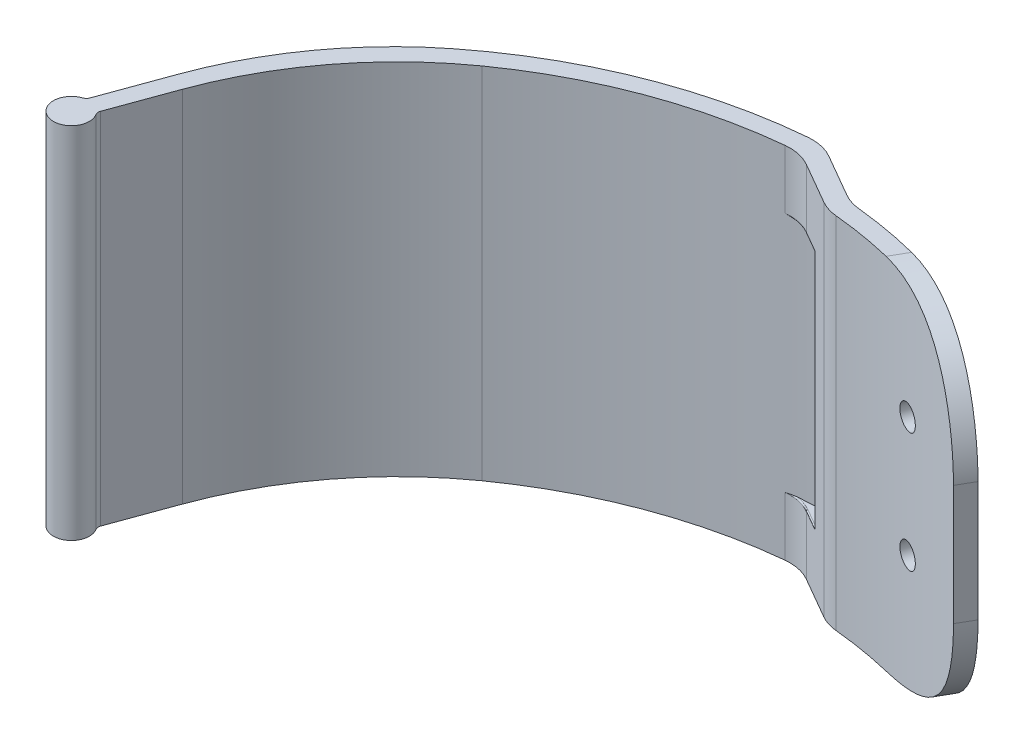
SolidWorks part; units mm, degrees
material "Silicon Rubber"
ref_plane "Front Plane" through (0, 0, 0) normal (0, 0, 1) x (1, 0, 0)
ref_plane "Top Plane" through (0, 0, 0) normal (0, 1, 0) x (1, 0, 0)
ref_plane "Right Plane" through (0, 0, 0) normal (1, 0, 0) x (0, 0, -1)
sketch "Sketch2" plane through (0, 0, 0) normal (0, 1, 0) x (1, 0, 0)
  line L0 (0, 0) -> (0, 40.4588) construction
  line L1 (0, 0) -> (-32.8892, 11.9707) construction
  line L2 (0, 0) -> (20.2294, 35.0384) construction
  line L3 (0, 0) -> (-20.2294, 35.0384) construction
  line L4 (-32.8892, 11.9707) -> (-38.0189, 13.8377) construction
  line L5 (-34.7493, 12.6477) -> (-36.1588, 13.1607) construction
  line L6 (-34.7493, 12.6477) -> (-34.9203, 12.1779)
  line L8 (-36.7997, 12.8619) -> (-34.4505, 12.0069) construction
  line L9 (-35.4541, 12.9042) -> (-36.159, 10.9673) construction
  line L10 (0, 0) -> (32.8892, 11.9707) construction
  line L11 (32.8892, 11.9707) -> (38.0189, 13.8377) construction
  line L12 (0, 36.9794) -> (0, 38.4794) construction
  line L13 (-2.4871, 39.1653) -> (2.4871, 36.2935) construction
  line L15 (-34.7493, 12.6477) -> (-31.1105, 22.6451)
  line L16 (0, 38.4794) -> (0, 39.9794) construction
  line L17 (0, 36.9794) -> (0, 35.4794) construction
  line L18 (-0.375, 37.0799) -> (0.375, 38.3789) construction
  line L19 (-2.284, 39.9141) -> (3.0118, 36.8566)
  line L20 (-2.6418, 38.3886) -> (2.5569, 35.3872)
  line L21 (18.4897, 32.0251) -> (17.7397, 30.7261)
  line L22 (-36.3298, 12.6909) -> (-32.4484, 23.3549)
  circle A0 centre (0, 0) radius 35 construction
  circle A1 centre (0, 0) radius 40.4588 construction
  arc A2 (-36.3298, 12.6909) -> (-36.6395, 12.3882) centre (-36.7997, 12.8619) cw
  arc A3 (-34.9203, 12.1779) -> (-34.8776, 11.747) centre (-34.4505, 12.0069) ccw
  arc A4 (-34.8776, 11.747) -> (-36.6395, 12.3882) centre (-36.159, 10.9673) cw
  arc A5 (35.4541, 12.9042) -> (-18.8647, 32.6746) centre (0, 0) ccw construction
  arc A6 (0, 38.4794) -> (-36.1588, 13.1607) centre (0, 0) ccw construction
  arc A7 (0, 39.9794) -> (-32.4484, 23.3549) centre (0, 0) ccw construction
  arc A8 (0, 36.9794) -> (18.4897, 32.0251) centre (0, 0) cw construction
  arc A9 (0, 35.4794) -> (17.7397, 30.7261) centre (0, 0) cw construction
  arc A10 (2.5569, 35.3872) -> (17.7397, 30.7261) centre (0, 0) cw
  arc A11 (3.0118, 36.8566) -> (18.4897, 32.0251) centre (0, 0) cw
  arc A12 (-31.1105, 22.6451) -> (-2.6418, 38.3886) centre (0, 0) cw
  arc A13 (-32.4484, 23.3549) -> (-2.284, 39.9141) centre (0, 0) cw
  point P12 (-35.4541, 12.9042)
  point P27 (0, 37.7294)
  point P30 (0, 37.7294)
  point P38 (0, 37.7294)
  dimension "D1" = 70
  dimension "D2" = 80.9177
  dimension "D8" = 0.5
  dimension "D9" = 0.5
  dimension "D10" = 1.5
  dimension "D3" = 70
  dimension "D4" = 30
  dimension "D5" = 30
  dimension "D6" = 1.5
  dimension "D11" = 70
  dimension "D12" = 1.5
  dimension "D13" = 60
  dimension "D14" = 1.5
  dimension "D15" = 1.5
  dimension "D16" = 1.5
  dimension "D7" = 0.5
extrude "Boss-Extrude1" add sketch "Sketch2" along normal blind 15 and the other way blind 15
sketch "Sketch3" plane through (0, 0, 0) normal (0, 1, 0) x (1, 0, 0)
  line L0 (-2.284, 39.9141) -> (3.0118, 36.8566) construction
  line L1 (-2.6418, 38.3886) -> (2.5569, 35.3872) construction
  line L2 (0.2019, 38.4789) -> (3.0118, 36.8566)
  line L3 (-2.6418, 38.3886) -> (-0.2, 36.9789)
  arc A0 (-2.6418, 38.3886) -> (0.2019, 38.4789) centre (0, 0) cw
  arc A1 (3.0118, 36.8566) -> (-0.2, 36.9789) centre (0, 0) ccw
extrude "Cut-Extrude1" cut sketch "Sketch3" against normal blind 10 and the other way blind 10
fillet "Fillet3" radius 3.75 6 edges at (2.5569, 0, -35.3872) (-2.6418, 12.5, -38.3886) (-2.6418, -12.5, -38.3886) (3.0118, -12.5, -36.8566) (-2.284, 0, -39.9141) (3.0118, 12.5, -36.8566)
fillet "Fillet4" radius 0.1 10 edges at (3.0203, 10, -36.9472) (1.2512, 10, -37.8731) (-0.9115, 10, -37.3896) (-2.7113, 10, -38.2194) (-0.9115, -10, -37.3896) (-2.7113, -10, -38.2194) (3.0203, -10, -36.9472) (1.2512, -10, -37.8731) (-0.2, 0, -36.9789) (0.2019, 0, -38.4789)
fillet "Fillet5" radius 30 2 edges at (-31.1105, 0, -22.6451) (-32.4484, 0, -23.3549)
sketch "Sketch4" plane through (0, 0, 0) normal (0, 1, 0) x (1, 0, 0)
  line L0 (0, 0) -> (0, 40.4588) construction
  line L1 (0, 0) -> (12.4138, 38.5073) construction
  circle A0 centre (0, 0) radius 40.4588 construction
  dimension "D1" = 17.868
ref_plane "Plane1" through (11.3462, 0, -35.1958) normal (0.3068, 0, -0.9518) x (-0.9518, 0, -0.3068)
sketch "Sketch7" plane through (11.3462, 0, -35.1958) normal (0.3068, 0, -0.9518) x (-0.9518, 0, -0.3068)
  line L0 (0, -5) -> (0, 5) construction
  circle A0 centre (0, 5) radius 1
  circle A1 centre (0, -5) radius 1
  point P4 (0, 0)
  dimension "D2" = 2
  dimension "D3" = 2
  dimension "D1" = 10
fillet "Fillet6" radius 10 2 edges at (18.1147, -15, -31.3756) (18.1147, 15, -31.3756)
sketch "Sketch8" plane through (11.3462, 0, -35.1958) normal (0.3068, 0, -0.9518) x (-0.9518, 0, -0.3068)
  line L0 (0, -5) -> (0, 5) construction
  circle A0 centre (0, 5) radius 2
  circle A1 centre (0, -5) radius 2
  point P4 (0, 0)
  dimension "D2" = 4
  dimension "D3" = 4
  dimension "D1" = 10
extrude "Cut-Extrude2" cut sketch "Sketch7" against normal through all
extrude "Cut-Extrude3" cut sketch "Sketch8" against normal blind 0.5
equation "\"Strap Thickness\"= 1.5mm"
equation "\"Strap Clamp Diameter\"= 3mm"
equation "\"Inner Diameter\"= 70mm"
equation "\"D1@Sketch2\"=\"Inner Diameter\""
equation "\"D6@Sketch2\"=\"Strap Thickness\""
equation "\"D10@Sketch2\"=\"Strap Clamp Diameter\" / 2"
equation "\"D12@Sketch2\"=\"Strap Thickness\""
equation "\"D14@Sketch2\"=\"Strap Thickness\""
equation "\"D15@Sketch2\"=\"Strap Thickness\""
equation "\"D16@Sketch2\"=\"Strap Thickness\""
equation "\"Band Width\"= 30mm"
equation "\"D1@Boss-Extrude1\"=\"Band Width\" / 2"
equation "\"D2@Boss-Extrude1\"=\"Band Width\" / 2"
